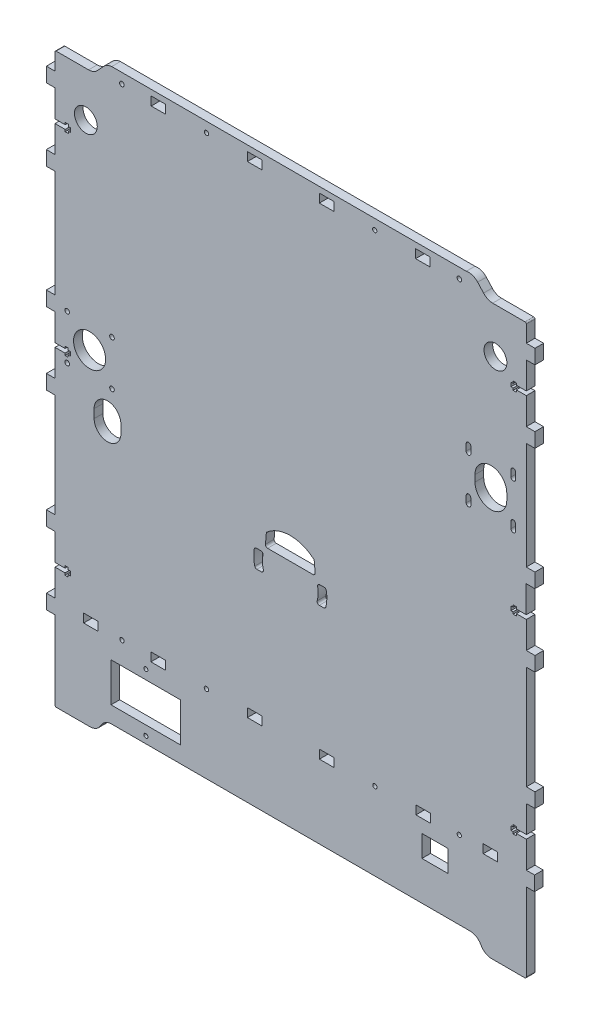
SolidWorks part; units mm, degrees
ref_plane "Спереди" through (0, 0, 0) normal (0, 0, 1) x (1, 0, 0)
ref_plane "Сверху" through (0, 0, 0) normal (0, 1, 0) x (1, 0, 0)
ref_plane "Справа" through (0, 0, 0) normal (1, 0, 0) x (0, 0, -1)
sketch "Эскиз1" plane through (0, 0, 0) normal (0, 0, 1) x (1, 0, 0)
  line L0 (-11.4163, -133.8634) -> (-21.4163, -133.8634)
  line L1 (-21.4163, -133.8634) -> (-21.4163, -127.8634)
  line L2 (-11.4163, -127.8634) -> (-11.4163, -133.8634)
  line L3 (-21.4163, -127.8634) -> (-11.4163, -127.8634)
  line L4 (-61.2563, -127.8634) -> (-61.2563, -133.8634)
  line L5 (-71.2563, -127.8634) -> (-61.2563, -127.8634)
  line L6 (-71.2563, -133.8634) -> (-71.2563, -127.8634)
  line L7 (-61.2563, -133.8634) -> (-71.2563, -133.8634)
  line L8 (49.4936, -157.9128) -> (49.4936, -142.9128)
  line L9 (49.4936, -142.9128) -> (67.4936, -142.9128)
  line L10 (67.4936, -142.9128) -> (67.4936, -157.9128)
  line L11 (67.4936, -157.9128) -> (49.4936, -157.9128)
  line L12 (-197.4876, 21.4243) -> (-197.4866, 20.0542)
  line L13 (-204.4363, 24.2766) -> (-204.4363, 42.8766)
  line L14 (-195.2876, 25.6494) -> (-195.2876, 25.6766)
  line L15 (127.7355, 42.8766) -> (127.7355, 52.8766)
  line L16 (-193.7868, 24.2485) -> (-193.7868, 24.2757)
  line L17 (-195.2868, 24.2757) -> (-195.2876, 25.6494)
  line L18 (-195.2868, 21.4269) -> (-195.2868, 21.4541)
  line L19 (-193.7868, 21.4541) -> (-193.7868, 24.2485)
  line L20 (112.6676, 24.3034) -> (112.6676, 24.2763)
  line L21 (114.8676, 24.3037) -> (114.8674, 25.6766)
  line L22 (-195.2868, 20.0542) -> (-195.2868, 21.4269)
  line L23 (111.1697, 21.5032) -> (111.1697, 21.4761)
  line L24 (111.1676, 24.2752) -> (111.1697, 21.5032)
  line L25 (121.7314, 24.2766) -> (121.7314, 42.8766)
  line L26 (-197.4876, 25.6494) -> (-197.4874, 24.2766)
  line L27 (127.7772, -7.1234) -> (127.7772, 2.8766)
  line L28 (112.6708, 20.1034) -> (112.6708, 20.0763)
  line L29 (-204.4363, 21.4566) -> (-204.4363, 21.4766)
  line L30 (121.7355, 52.8766) -> (121.7355, 127.0366)
  line L31 (-210.4363, 42.8766) -> (-210.4363, 52.8766)
  line L32 (-204.4363, 2.8766) -> (-204.4363, 21.4566)
  line L33 (-204.4363, 52.8766) -> (-204.4363, 127.0366)
  line L34 (-128.0563, -133.8634) -> (-138.0563, -133.8634)
  line L35 (-138.0563, -133.8634) -> (-138.0563, -127.8634)
  line L36 (-138.0563, -127.8634) -> (-128.0563, -127.8634)
  line L37 (-128.0563, -127.8634) -> (-128.0563, -133.8634)
  line L38 (-174.6363, -133.8634) -> (-184.6363, -133.8634)
  line L39 (-184.6363, -133.8634) -> (-184.6363, -127.8634)
  line L40 (-184.6363, -127.8634) -> (-174.6363, -127.8634)
  line L41 (-174.6363, -127.8634) -> (-174.6363, -133.8634)
  line L42 (91.9637, -133.8634) -> (101.9637, -133.8634)
  line L43 (101.9637, -133.8634) -> (101.9637, -127.8634)
  line L44 (101.9637, -127.8634) -> (91.9637, -127.8634)
  line L45 (91.9637, -127.8634) -> (91.9637, -133.8634)
  line L46 (55.3837, -133.8634) -> (45.3837, -133.8634)
  line L47 (45.3837, -133.8634) -> (45.3837, -127.8634)
  line L48 (45.3837, -127.8634) -> (55.3837, -127.8634)
  line L49 (55.3837, -127.8634) -> (55.3837, -133.8634)
  line L50 (-18.1346, -29.194) -> (-21.1843, -29.194)
  line L51 (-21.5365, -41.694) -> (-18.4403, -41.694)
  line L52 (-64.7445, -41.694) -> (-61.6484, -41.694)
  line L53 (-62.0005, -29.194) -> (-65.0502, -29.194)
  line L54 (-58.1883, -16.8245) -> (-58.7957, -23.7669)
  line L55 (-24.3892, -23.7669) -> (-24.9965, -16.8245)
  line L56 (-57.3014, -25.3976) -> (-25.8835, -25.3976)
  line L57 (-165.6924, -146.4128) -> (-165.6924, -173.4128)
  line L58 (-165.6924, -173.4128) -> (-117.6924, -173.4128)
  line L59 (-117.6924, -173.4128) -> (-117.6924, -146.4128)
  line L60 (-117.6924, -146.4128) -> (-165.6924, -146.4128)
  line L61 (-181.2137, 199.4366) -> (-203.6703, 199.4366)
  line L62 (-170.8491, 206.6945) -> (-174.9446, 202.2149)
  line L63 (127.478, -128.8434) -> (121.7637, -128.8434)
  line L64 (80.2335, 209.4366) -> (-165.1973, 209.4366)
  line L65 (121.7772, -7.1234) -> (127.7772, -7.1234)
  line L66 (88.0955, 206.8296) -> (92.1957, 202.3542)
  line L67 (98.4674, 199.4366) -> (120.8437, 199.4366)
  line L68 (121.7637, 187.0366) -> (121.7637, 198.5166)
  line L69 (121.7637, 177.0366) -> (127.7637, 177.0366)
  line L70 (127.7637, 177.0366) -> (127.7637, 187.0366)
  line L71 (-204.4363, 42.8766) -> (-210.4363, 42.8766)
  line L72 (120.8067, -193.8634) -> (97.8063, -193.8634)
  line L73 (91.3771, -190.805) -> (89.3204, -187.7854)
  line L74 (-203.3585, -193.8634) -> (-180.2324, -193.8634)
  line L75 (-210.4363, 177.0366) -> (-210.4363, 187.0366)
  line L76 (114.8517, 158.4366) -> (114.8517, 159.8367)
  line L77 (121.8652, -107.4334) -> (114.8652, -107.4334)
  line L78 (-204.4363, 158.4366) -> (-204.4363, 177.0366)
  line L79 (114.8652, -106.0333) -> (112.6643, -106.0333)
  line L80 (-204.4363, -107.4334) -> (-204.4363, -88.8534)
  line L81 (114.8709, -110.2334) -> (121.7637, -110.2334)
  line L82 (121.8652, -107.4334) -> (121.8652, -88.8534)
  line L83 (111.1668, -110.2331) -> (112.6668, -110.2322)
  line L84 (112.6643, -106.0333) -> (112.6652, -107.4331)
  line L85 (111.1652, -107.434) -> (111.1668, -110.2331)
  line L86 (-197.5237, -111.681) -> (-195.335, -111.6794)
  line L87 (121.7637, 158.4366) -> (114.8517, 158.4366)
  line L88 (114.8708, -111.6332) -> (114.8709, -110.2334)
  line L89 (114.8652, -107.4334) -> (114.8652, -106.0333)
  line L90 (112.6652, -107.4331) -> (111.1652, -107.434)
  line L91 (112.6533, 155.6378) -> (112.6541, 154.2369)
  line L92 (-197.4908, -105.897) -> (-197.4906, -107.4334)
  line L93 (-204.4363, 21.4766) -> (-197.4876, 21.4766)
  line L94 (-197.4876, 21.4766) -> (-197.4876, 21.4243)
  line L95 (-204.4363, 155.6366) -> (-197.3871, 155.6366)
  line L96 (121.7637, -128.8434) -> (121.7637, -110.2334)
  line L97 (121.7801, 2.8766) -> (121.7801, 21.4766)
  line L98 (127.478, -138.8434) -> (127.478, -128.8434)
  line L99 (114.8706, 21.4766) -> (121.7801, 21.4766)
  line L100 (-197.3871, 155.6366) -> (-197.3871, 154.2365)
  line L101 (-197.4181, 158.4366) -> (-204.4363, 158.4366)
  line L102 (-195.2181, 158.419) -> (-195.2181, 159.8366)
  line L103 (112.6668, -110.2322) -> (112.6676, -111.6331)
  line L104 (-197.4906, -107.4334) -> (-204.4363, -107.4334)
  line L105 (112.6508, 159.8367) -> (112.6517, 158.4369)
  line L106 (114.8541, 154.2368) -> (114.8542, 155.6366)
  line L107 (-197.5239, -110.2334) -> (-197.5237, -111.681)
  line L108 (111.1517, 158.436) -> (111.1533, 155.6369)
  line L109 (-195.2876, 25.6766) -> (-197.4876, 25.6766)
  line L110 (112.6708, 20.0763) -> (114.8708, 20.0766)
  line L111 (112.6541, 154.2369) -> (114.8541, 154.2368)
  line L112 (111.1533, 155.6369) -> (112.6533, 155.6378)
  line L113 (121.7772, -78.8534) -> (121.7772, -7.1234)
  line L114 (-195.1863, 155.619) -> (-193.7155, 155.619)
  line L115 (112.6666, 25.6762) -> (112.6676, 24.3034)
  line L116 (114.8676, 24.2766) -> (114.8676, 24.3037)
  line L117 (112.6517, 158.4369) -> (111.1517, 158.436)
  line L118 (-195.3299, -105.8955) -> (-197.4908, -105.897)
  line L119 (-193.6779, -110.2778) -> (-193.6833, -107.2844)
  line L120 (-195.3368, -110.2798) -> (-193.6779, -110.2778)
  line L121 (-197.4866, 20.0542) -> (-195.2868, 20.0542)
  line L122 (-195.2868, 21.4541) -> (-193.7868, 21.4541)
  line L123 (114.8708, 20.0766) -> (114.8708, 20.1037)
  line L124 (-204.4363, -110.2334) -> (-197.5239, -110.2334)
  line L125 (-195.3281, -107.2865) -> (-195.3299, -105.8955)
  line L126 (-193.7868, 24.2757) -> (-195.2868, 24.2757)
  line L127 (-197.3871, 154.2365) -> (-195.1863, 154.2365)
  line L128 (-195.335, -111.6794) -> (-195.3368, -110.2798)
  line L129 (-197.4181, 159.8366) -> (-197.4181, 158.4366)
  line L130 (-193.6833, -107.2844) -> (-195.3281, -107.2865)
  line L131 (-195.1863, 154.2365) -> (-195.1863, 155.619)
  line L133 (114.8517, 159.8367) -> (112.6508, 159.8367)
  line L134 (-193.7155, 155.619) -> (-193.7155, 158.419)
  line L135 (114.8542, 155.6366) -> (121.7637, 155.6366)
  line L136 (-197.4874, 24.2766) -> (-204.4363, 24.2766)
  line L137 (114.8708, 20.1037) -> (114.8706, 21.4766)
  line L138 (-197.4876, 25.6766) -> (-197.4876, 25.6494)
  line L139 (112.6676, -111.6331) -> (114.8708, -111.6332)
  line L140 (112.6676, 24.2763) -> (111.1676, 24.2752)
  line L141 (-195.2181, 159.8366) -> (-197.4181, 159.8366)
  line L142 (121.7637, 158.4366) -> (121.7637, 177.0366)
  line L143 (114.8674, 25.6766) -> (112.6666, 25.6762)
  line L144 (-193.7155, 158.419) -> (-195.2181, 158.419)
  line L145 (-204.4363, -7.1234) -> (-210.4363, -7.1234)
  line L146 (-204.4363, 177.0366) -> (-210.4363, 177.0366)
  line L147 (127.7772, -88.8534) -> (127.7772, -78.8534)
  line L148 (111.1697, 21.4761) -> (112.6697, 21.4772)
  line L149 (121.7314, 24.2766) -> (114.8676, 24.2766)
  line L150 (112.6697, 21.4772) -> (112.6708, 20.1034)
  line L151 (-204.4363, -192.8001) -> (-204.4363, -138.8434)
  line L152 (-204.4363, 137.0366) -> (-204.4363, 155.6366)
  line L153 (-210.4363, 127.0366) -> (-210.4363, 137.0366)
  line L154 (-204.4363, 127.0366) -> (-210.4363, 127.0366)
  line L155 (127.7355, 127.0366) -> (127.7355, 137.0366)
  line L156 (127.7355, 137.0366) -> (121.7637, 137.0366)
  line L157 (-137.8416, 205.4366) -> (-127.8416, 205.4366)
  line L158 (-127.8416, 205.4366) -> (-127.8416, 199.4366)
  line L159 (-127.8416, 199.4366) -> (-137.8416, 199.4366)
  line L160 (-137.8416, 199.4366) -> (-137.8416, 205.4366)
  line L161 (55.1584, 199.4366) -> (45.1584, 199.4366)
  line L162 (45.1584, 199.4366) -> (45.1584, 205.4366)
  line L163 (45.1584, 205.4366) -> (55.1584, 205.4366)
  line L164 (55.1584, 205.4366) -> (55.1584, 199.4366)
  line L165 (-61.2416, 199.4366) -> (-71.2416, 199.4366)
  line L166 (-71.2416, 199.4366) -> (-71.2416, 205.4366)
  line L167 (-71.2416, 205.4366) -> (-61.2416, 205.4366)
  line L169 (-11.4416, 199.4366) -> (-21.4416, 199.4366)
  line L170 (-21.4416, 199.4366) -> (-21.4416, 205.4366)
  line L171 (-21.4416, 205.4366) -> (-11.4416, 205.4366)
  line L173 (127.7637, 187.0366) -> (121.7637, 187.0366)
  line L174 (121.7637, 137.0366) -> (121.7637, 155.6366)
  line L175 (121.7355, 127.0366) -> (127.7355, 127.0366)
  line L176 (-210.4363, 2.8766) -> (-204.4363, 2.8766)
  line L177 (-204.4363, -128.8434) -> (-204.4363, -110.2334)
  line L178 (-204.4363, -78.8534) -> (-204.4363, -7.1234)
  line L179 (-210.4311, -128.8434) -> (-204.4363, -128.8434)
  line L180 (-210.4363, -88.8534) -> (-210.4363, -78.8534)
  line L181 (-210.4363, -7.1234) -> (-210.4363, 2.8766)
  line L182 (-210.4363, -78.8534) -> (-204.4363, -78.8534)
  line L183 (-173.7242, -190.8095) -> (-171.6691, -187.7888)
  line L184 (127.7355, 52.8766) -> (121.7355, 52.8766)
  line L185 (121.7637, -192.6916) -> (121.7637, -138.8434)
  line L186 (-165.1593, -184.7491) -> (82.809, -184.7491)
  line L187 (-210.4311, -138.8434) -> (-210.4311, -128.8434)
  line L188 (-204.4363, -138.8434) -> (-210.4311, -138.8434)
  line L189 (-210.4363, 137.0366) -> (-204.4363, 137.0366)
  line L190 (-210.4363, 187.0366) -> (-204.4363, 187.0366)
  line L191 (-210.4363, 52.8766) -> (-204.4363, 52.8766)
  line L192 (-204.4363, -88.8534) -> (-210.4363, -88.8534)
  line L193 (121.7637, -138.8434) -> (127.478, -138.8434)
  line L194 (127.7772, -78.8534) -> (121.7772, -78.8534)
  line L195 (127.7772, 2.8766) -> (121.7801, 2.8766)
  line L196 (-204.4363, 187.0366) -> (-204.4363, 198.2588)
  line L197 (121.7314, 42.8766) -> (127.7355, 42.8766)
  line L198 (121.8652, -88.8534) -> (127.7772, -88.8534)
  line L199 (-158.8564, -7.694) -> (-158.8564, -1.694)
  line L200 (86.2572, 90.556) -> (86.2572, 86.056)
  line L201 (111.1572, 75.056) -> (111.1572, 70.556)
  line L202 (108.2572, 86.056) -> (108.2572, 90.556)
  line L203 (114.3572, 101.556) -> (114.3572, 106.056)
  line L204 (111.1572, 106.056) -> (111.1572, 101.556)
  line L205 (114.3572, 70.556) -> (114.3572, 75.056)
  line L206 (80.1572, 75.056) -> (80.1572, 70.556)
  line L207 (83.3572, 70.556) -> (83.3572, 75.056)
  line L208 (83.3572, 101.556) -> (83.3572, 106.056)
  line L209 (-177.3564, -1.694) -> (-177.3564, -7.694)
  line L210 (80.1572, 106.056) -> (80.1572, 101.556)
  line L211 (-61.2416, 205.4366) -> (-61.2416, 199.4366)
  line L212 (-11.4416, 199.4366) -> (-11.4416, 205.4366)
  line L213 (-141.5552, -189.1404) -> (-141.5552, -133.1187) construction
  line L214 (-195.203, -133.8634) -> (114.843, -133.8634) construction
  line L215 (-204.4363, 213.0066) -> (-204.4363, -217.9418) construction
  line L216 (121.7637, 210.9354) -> (121.7637, -201.1521) construction
  arc A0 (80.1572, 70.556) -> (83.3572, 70.556) centre (81.7572, 70.556) ccw
  arc A1 (80.1572, 101.556) -> (83.3572, 101.556) centre (81.7572, 101.556) ccw
  circle A2 centre (-183.0863, 168.4366) radius 7.9
  circle A3 centre (100.4084, 168.4366) radius 7.9
  arc A4 (-16.6559, -30.4419) -> (-18.1346, -29.194) centre (-18.1346, -30.694) ccw
  arc A5 (-21.1843, -29.194) -> (-22.6563, -30.9825) centre (-21.1843, -30.694) ccw
  arc A6 (-22.9831, -39.7973) -> (-22.6563, -30.9825) centre (-41.5924, -34.694) ccw
  arc A7 (-22.9831, -39.7973) -> (-21.5365, -41.694) centre (-21.5365, -40.194) ccw
  arc A8 (-65.0502, -29.194) -> (-66.5289, -30.4419) centre (-65.0502, -30.694) ccw
  arc A9 (-66.5289, -30.4419) -> (-66.2039, -40.5407) centre (-41.5924, -34.694) ccw
  arc A10 (-66.2039, -40.5407) -> (-64.7445, -41.694) centre (-64.7445, -40.194) ccw
  arc A11 (-61.6484, -41.694) -> (-60.2018, -39.7973) centre (-61.6484, -40.194) ccw
  arc A12 (-60.5285, -30.9825) -> (-60.2018, -39.7973) centre (-41.5924, -34.694) ccw
  arc A13 (-60.5285, -30.9825) -> (-62.0005, -29.194) centre (-62.0005, -30.694) ccw
  arc A14 (-16.9809, -40.5407) -> (-16.6559, -30.4419) centre (-41.5924, -34.694) ccw
  arc A15 (-18.4403, -41.694) -> (-16.9809, -40.5407) centre (-18.4403, -40.194) ccw
  arc A16 (-57.6664, -15.8131) -> (-58.1883, -16.8245) centre (-56.694, -16.9552) ccw
  arc A17 (-25.5185, -15.8131) -> (-57.6664, -15.8131) centre (-41.5924, -34.694) ccw
  arc A18 (-24.9965, -16.8245) -> (-25.5185, -15.8131) centre (-26.4908, -16.9552) ccw
  arc A19 (-25.8835, -25.3976) -> (-24.3892, -23.7669) centre (-25.8835, -23.8976) ccw
  arc A20 (-58.7957, -23.7669) -> (-57.3014, -25.3976) centre (-57.3014, -23.8976) ccw
  circle A21 centre (-158.1416, 202.4366) radius 1.6
  arc A22 (-203.6703, 199.4366) -> (-204.4363, 198.2588) centre (-203.5603, 198.5271) ccw
  arc A23 (-181.2137, 199.4366) -> (-174.9446, 202.2149) centre (-181.2321, 207.9403) ccw
  arc A24 (-165.1973, 209.4366) -> (-170.8491, 206.6945) centre (-164.5754, 200.9594) ccw
  circle A25 centre (75.4584, 202.4366) radius 1.6
  arc A26 (88.0955, 206.8296) -> (80.2335, 209.4366) centre (81.8282, 201.0876) ccw
  arc A27 (-180.2324, -193.8634) -> (-173.7242, -190.8095) centre (-180.2521, -185.3595) ccw
  arc A28 (120.8067, -193.8634) -> (121.7637, -192.6916) centre (120.6617, -192.7683) ccw
  arc A29 (-165.1593, -184.7491) -> (-171.6691, -187.7888) centre (-165.1549, -193.2491) ccw
  arc A30 (-204.4363, -192.8001) -> (-203.3585, -193.8634) centre (-203.4855, -192.9141) ccw
  arc A31 (89.3204, -187.7854) -> (82.809, -184.7491) centre (82.809, -193.2491) ccw
  arc A32 (91.3771, -190.805) -> (97.8063, -193.8634) centre (97.8839, -185.4133) ccw
  arc A34 (92.1957, 202.3542) -> (98.4674, 199.4366) centre (98.6272, 207.9796) ccw
  circle A35 centre (16.8584, 202.4366) radius 1.5
  circle A36 centre (-99.5416, 202.4366) radius 1.5
  circle A37 centre (-196.0064, 47.306) radius 1.6
  arc A38 (-177.3564, -7.694) -> (-158.8564, -7.694) centre (-168.1064, -7.694) ccw
  circle A39 centre (-165.0064, 16.306) radius 1.6
  circle A40 centre (-196.0064, 16.306) radius 1.6
  arc A41 (86.2572, 86.056) -> (108.2572, 86.056) centre (97.2572, 86.056) ccw
  arc A42 (108.2572, 90.556) -> (86.2572, 90.556) centre (97.2572, 90.556) ccw
  arc A43 (114.3572, 75.056) -> (111.1572, 75.056) centre (112.7572, 75.056) ccw
  circle A44 centre (-180.5064, 31.806) radius 11.1
  circle A45 centre (-165.0064, 47.306) radius 1.6
  arc A46 (114.3572, 106.056) -> (111.1572, 106.056) centre (112.7572, 106.056) ccw
  arc A47 (111.1572, 101.556) -> (114.3572, 101.556) centre (112.7572, 101.556) ccw
  arc A48 (111.1572, 70.556) -> (114.3572, 70.556) centre (112.7572, 70.556) ccw
  arc A49 (83.3572, 75.056) -> (80.1572, 75.056) centre (81.7572, 75.056) ccw
  arc A50 (-158.8564, -1.694) -> (-177.3564, -1.694) centre (-168.1064, -1.694) ccw
  arc A51 (83.3572, 106.056) -> (80.1572, 106.056) centre (81.7572, 106.056) ccw
  circle A52 centre (75.3837, -130.8634) radius 1.5
  circle A53 centre (16.9837, -130.8634) radius 1.5
  circle A54 centre (-99.6563, -130.8634) radius 1.5
  circle A55 centre (-158.0563, -130.8634) radius 1.5
  arc A57 (121.7637, 198.5166) -> (120.8437, 199.4366) centre (120.8437, 198.5166) ccw
  circle A58 centre (-141.5552, -179.9491) radius 1.4
  circle A59 centre (-141.5552, -139.9491) radius 1.4
  point P319 (-207.4363, 187.0366)
  point P322 (-11.4416, 202.4366)
  point P326 (-249.5335, 180.3765)
  point P330 (-21.4163, -130.8634)
  point P331 (55.3837, -130.8634)
  point P336 (88.0392, -135.7474)
  point P337 (-49.2762, 46.3401)
  dimension "D1" = 15.8
  dimension "D2" = 15.8
  dimension "D3" = 22.2
  dimension "D6" = 19.8
  dimension "D96" = 2.8
  dimension "D97" = 2.8
  dimension "D4" = 403.3
  dimension "D7" = 326.2
  dimension "D10" = 12.4
  dimension "D11" = 10
  dimension "D13" = 6
  dimension "D14" = 19.8
  dimension "D15" = 4
  dimension "D16" = 7
  dimension "D17" = 7
  dimension "D18" = 4
  dimension "D19" = 4
  dimension "D20" = 7
  dimension "D21" = 7
  dimension "D22" = 4
  dimension "D23" = 6
  dimension "D24" = 28.3
  dimension "D25" = 28.3
  dimension "D26" = 28.3
  dimension "D27" = 39.84
  dimension "D28" = 10
  dimension "D29" = 10
  dimension "D30" = 10
  dimension "D31" = 10
  dimension "D33" = 21.35
  dimension "D36" = 6
  dimension "D37" = 6
  dimension "D39" = 28.3
  dimension "D41" = 31
  dimension "D45" = 18.6
  dimension "D47" = 2.8
  dimension "D48" = 18.6
  dimension "D50" = 10
  dimension "D57" = 31
  dimension "D58" = 31
  dimension "D83" = 71.73
  dimension "D84" = 10
  dimension "D85" = 6
  dimension "D88" = 6
  dimension "D89" = 18.58
  dimension "D90" = 2.8
  dimension "D98" = 4.8
  dimension "D99" = 44.8
  dimension "D100" = 60
  dimension "D101" = 6
  dimension "D102" = 10
  dimension "D103" = 3
  dimension "D104" = 6
  dimension "D105" = 10
  dimension "D106" = 3
  dimension "D107" = 6
  dimension "D108" = 10
  dimension "D109" = 6
  dimension "D110" = 10
  dimension "D111" = 3
  dimension "D112" = 6
  dimension "D113" = 10
  dimension "D114" = 3
  dimension "D115" = 6
  dimension "D116" = 10
  dimension "D118" = 16.58
  dimension "D119" = 20
  dimension "D120" = 28.4
  dimension "D121" = 28.4
  dimension "D123" = 16.58
  dimension "D124" = 20
  dimension "D125" = 28.4
  dimension "D126" = 28.4
extrude "Бобышка-Вытянуть1" add sketch "Эскиз1" along normal blind 6
